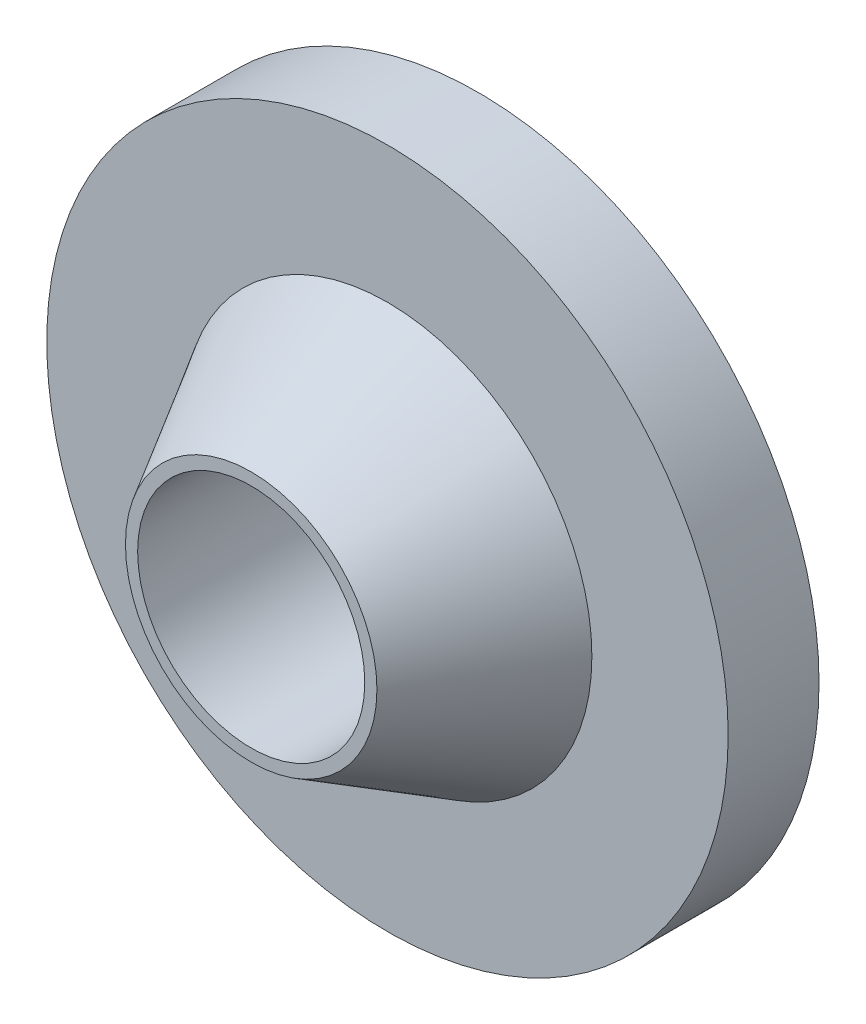
SolidWorks part; units mm, degrees
ref_plane "Front Plane" through (0, 0, 0) normal (0, 0, 1) x (1, 0, 0)
ref_plane "Top Plane" through (0, 0, 0) normal (0, 1, 0) x (1, 0, 0)
ref_plane "Right Plane" through (0, 0, 0) normal (1, 0, 0) x (0, 0, -1)
sketch "Sketch1" plane through (0, 0, 0) normal (0, 0, 1) x (1, 0, 0)
  circle A0 centre (0, 0) radius 7.5
  circle A1 centre (0, 0) radius 2.5
  dimension "D1" = 15
  dimension "D2" = 5
extrude "Boss-Extrude1" add sketch "Sketch1" along normal blind 2
sketch "Sketch2" plane through (0, 0, 2) normal (0, 0, 1) x (1, 0, 0)
  circle A0 centre (0, 0) radius 2.5
  circle A1 centre (0, 0) radius 4.5
  dimension "D1" = 9
extrude "Boss-Extrude2" add sketch "Sketch2" along normal blind 3
chamfer "Chamfer1" distance 3 angle 30 1 edges at (4.5, 0, 5) first distance on face at (4.5, 0, 5)
